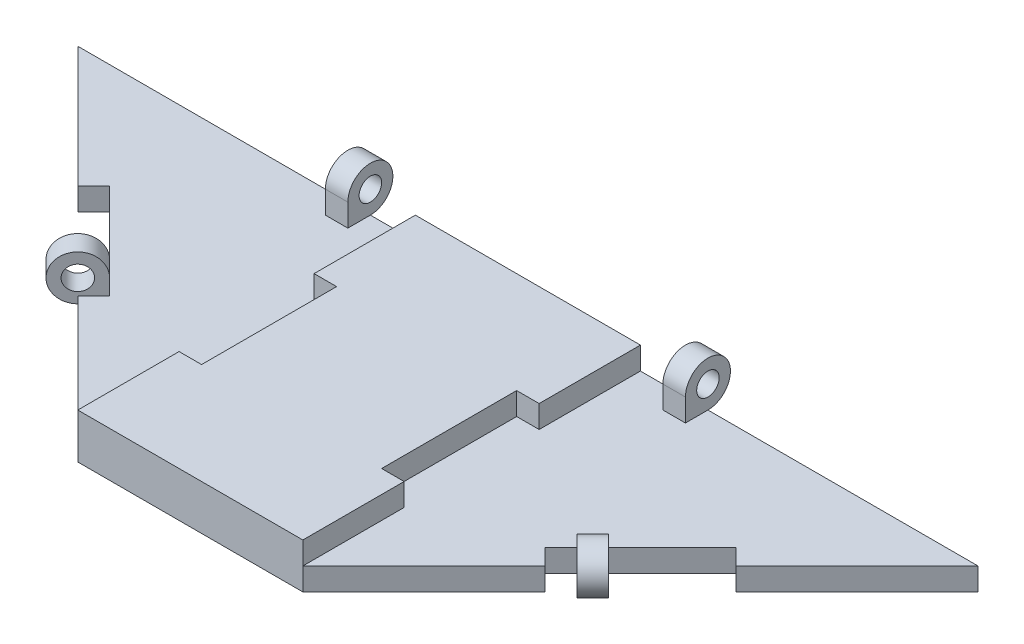
SolidWorks part; units mm, degrees
material "PET"
ref_plane "Front Plane" through (0, 0, 0) normal (0, 0, 1) x (1, 0, 0)
ref_plane "Top Plane" through (0, 0, 0) normal (0, 1, 0) x (1, 0, 0)
ref_plane "Right Plane" through (0, 0, 0) normal (1, 0, 0) x (0, 0, -1)
sketch "Sketch1" plane through (0, 0, 0) normal (0, 1, 0) x (1, 0, 0)
  line L0 (-25, 25) -> (-100, 100)
  line L1 (-100, 100) -> (100, 100)
  line L2 (100, 100) -> (25, 25)
  line L3 (25, 25) -> (-25, 25)
  line L4 (0, 0) -> (0, 115.119) construction
  dimension "D1" = 45
  dimension "D2" = 200
  dimension "D3" = 50
extrude "Boss-Extrude1" add sketch "Sketch1" along normal blind 10
sketch "Sketch2" plane through (0, 10, 0) normal (0, 1, 0) x (1, 0, 0)
  line L0 (-25, 47.5) -> (-25, 77.5)
  line L1 (-25, 47.5) -> (-20, 47.5)
  line L2 (-25, 77.5) -> (-20, 77.5)
  line L3 (-20, 47.5) -> (-20, 77.5)
  line L4 (100, 100) -> (-100, 100) construction
  line L5 (-73.1066, 73.1066) -> (-51.8934, 51.8934)
  line L6 (-73.1066, 73.1066) -> (-69.5711, 76.6421)
  line L7 (-51.8934, 51.8934) -> (-48.3579, 55.4289)
  line L8 (-69.5711, 76.6421) -> (-48.3579, 55.4289)
  line L9 (-100, 100) -> (-25, 25) construction
  line L10 (-62.5, 62.5) -> (-54.9042, 70.0958) construction
  line L11 (-25, 62.5) -> (-7.0873, 62.5) construction
  line L12 (-25, 25) -> (-25, 100)
  line L13 (-25, 100) -> (-100, 100)
  line L14 (-100, 100) -> (-25, 25)
  line M11 (100, 100) -> (-100, 100)
  line M12 (-100, 100) -> (-25, 25)
  dimension "D1" = 30
  dimension "D2" = 5
  dimension "D3" = 30
  dimension "D4" = 5
extrude "Cut-Extrude1" cut sketch "Sketch2" against normal blind 5 contours L12 L0 L6 L8 L7 M12 M11 | L1 L3 L2 L0 region at (-49.3954, 10, -75.6046) region at (-22.5, 10, -62.5)
extrude "Cut-Extrude2" cut sketch "Sketch2<4>" against normal up to next contours L8 L6 L7 M12 region at (-60.7322, 10, -64.2678)
sketch "Sketch2<4>" plane through (0, 10, 0) normal (0, 1, 0) x (1, 0, 0) same geometry as "Sketch2"
sketch "Sketch3" plane through (-51.8934, 0, -51.8934) normal (-0.7071, 0, -0.7071) x (-0.7071, 0, 0.7071)
  circle A0 centre (0, 5) radius 5
  circle A1 centre (0, 5) radius 2.6345
  line M1 (0, 0) -> (0, 5)
  line M2 (0, 5) -> (-5, 5)
  line M3 (-5, 5) -> (-5, 0)
  line M4 (-5, 0) -> (0, 0)
  dimension "D1" = 5.269
extrude "Boss-Extrude2" add sketch "Sketch3" along normal blind 5 from offset 5 contours A0 M3 M4 | A1 A0 M2 M1 | A1 A0 M1 M2 region at (-54.3227, 1.5645, -49.4641) region at (-50.12, 2.4921, -53.6668) region at (-49.1476, 1.1168, -54.6392)
sketch "Sketch4" plane through (-25, 0, 0) normal (-1, 0, 0) x (0, 0, 1)
  line L0 (-95, 10) -> (-95, 5)
  line L1 (-77.5, 5) -> (-100, 5) construction
  line L2 (-95, 5) -> (-100, 5)
  circle A0 centre (-100, 10) radius 5
  circle A1 centre (-100, 10) radius 2.5
  line M1 (-77.5, 10) -> (-100, 10)
  line M2 (-100, 10) -> (-100, 5)
  line M3 (-100, 5) -> (-77.5, 5)
  dimension "D1" = 5
extrude "Boss-Extrude3" add sketch "Sketch4" along normal blind 5 from offset 10 contours A1 A0 M2 M1 | A0 L0 M3 | A1 A0 M1 M2 region at (-25, 10.1414, -96.25) region at (-25, 6.1168, -96.1168) region at (-25, 7.5243, -97.5243)
mirror "Mirror1" about plane through (0, 0, 0) normal (1, 0, 0) of "Boss-Extrude3", "Cut-Extrude2", "Cut-Extrude1", "Boss-Extrude2"
